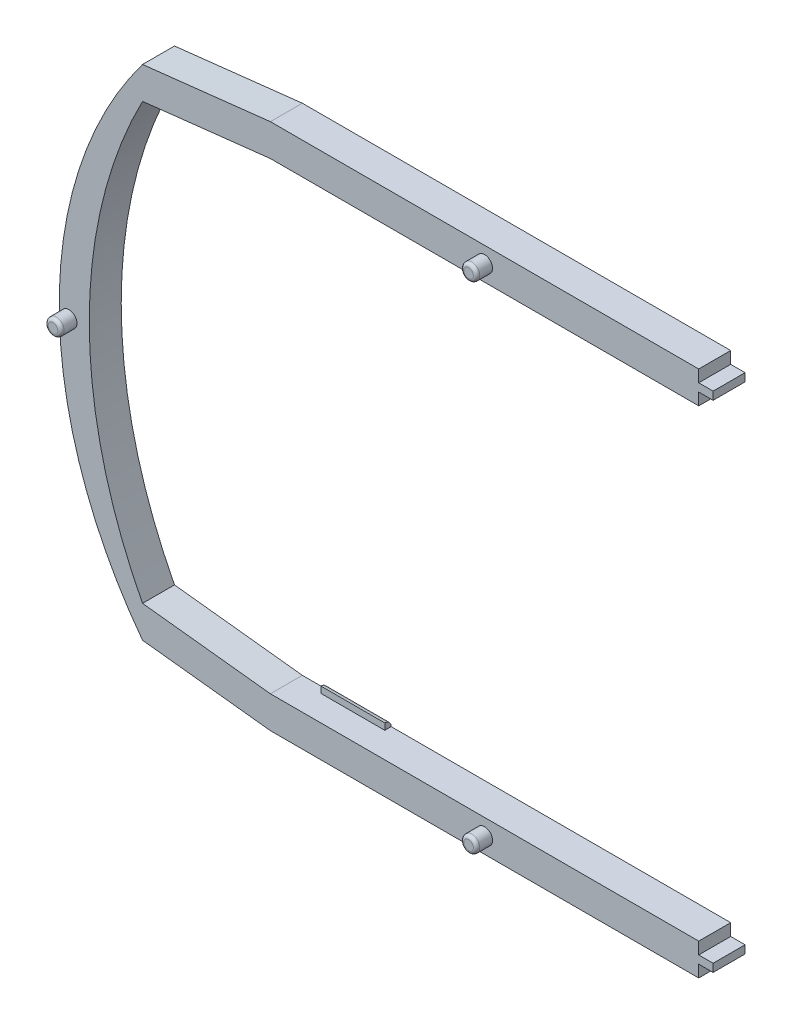
SolidWorks part; units mm, degrees
ref_plane "Plan de face" through (0, 0, 0) normal (0, 0, 1) x (1, 0, 0)
ref_plane "Plan de dessus" through (0, 0, 0) normal (0, 1, 0) x (1, 0, 0)
ref_plane "Plan de droite" through (0, 0, 0) normal (1, 0, 0) x (0, 0, -1)
sketch "Esquisse1" plane through (0, 0, 0) normal (0, 0, 1) x (1, 0, 0)
  line L0 (-191.5944, 34.0601) -> (-151.5944, 38.5601)
  line L1 (-151.5944, 38.5601) -> (-17.5944, 38.5601)
  line L2 (-151.5944, 38.5601) -> (-151.5944, -106.4399)
  line L3 (-151.5944, -106.4399) -> (-17.5944, -106.4399)
  line L4 (-17.5944, 38.5601) -> (-17.5944, -106.4399)
  line L5 (-151.5944, 38.5601) -> (-191.5944, 38.5601)
  line L6 (-151.5944, 48.5601) -> (-151.5944, -106.4399)
  line L7 (-151.5944, 38.5601) -> (-151.5944, -106.4399)
  line L8 (-151.5944, -106.4399) -> (-191.5944, -106.4399)
  line L9 (-191.5944, 38.5601) -> (-191.5944, -106.4399)
  line L10 (-151.5944, 38.5601) -> (-191.5944, 38.5601)
  line L11 (-151.5944, 38.5601) -> (-151.5944, 34.0601)
  line L12 (-151.5944, 34.0601) -> (-191.5944, 34.0601)
  line L13 (-191.5944, 38.5601) -> (-191.5944, 34.0601)
  line L14 (-151.5944, -106.4399) -> (-191.5944, -106.4399)
  line L15 (-151.5944, -106.4399) -> (-151.5944, -101.9399)
  line L16 (-151.5944, -101.9399) -> (-191.5944, -101.9399)
  line L17 (-191.5944, -106.4399) -> (-191.5944, -101.9399)
  line L18 (-191.5944, -101.9399) -> (-151.5944, -106.4399)
  line L19 (-151.5944, 48.5601) -> (-191.5944, 44.0601)
  line L20 (-151.5944, 38.5601) -> (-17.5944, 38.5601)
  line L21 (-151.5944, 38.5601) -> (-151.5944, 48.5601)
  line L22 (-151.5944, 48.5601) -> (-17.5944, 48.5601)
  line L23 (-17.5944, 38.5601) -> (-17.5944, 48.5601)
  line L24 (-143.8059, 38.5601) -> (-123.8059, 38.5601)
  line L25 (-143.8059, 38.5601) -> (-143.8059, 36.5601)
  line L26 (-143.8059, 36.5601) -> (-123.8059, 36.5601)
  line L27 (-123.8059, 38.5601) -> (-123.8059, 36.5601)
  line L28 (-143.8059, -106.4399) -> (-123.8059, -106.4399)
  line L29 (-143.8059, -106.4399) -> (-143.8059, -104.4399)
  line L30 (-143.8059, -104.4399) -> (-123.8059, -104.4399)
  line L31 (-123.8059, -106.4399) -> (-123.8059, -104.4399)
  line L32 (-151.5944, -106.4399) -> (-17.5944, -106.4399)
  line L33 (-151.5944, -106.4399) -> (-151.5944, -116.4399)
  line L34 (-151.5944, -116.4399) -> (-17.5944, -116.4399)
  line L35 (-17.5944, -106.4399) -> (-17.5944, -116.4399)
  line L36 (-191.5944, 44.0601) -> (-191.5944, 34.0601)
  line L37 (-191.5944, 44.0601) -> (-191.5944, 38.5601)
  line L38 (-151.5944, -116.4399) -> (-191.5944, -111.9399)
  line L39 (-191.5944, -111.9399) -> (-191.5944, -106.4399)
  line L41 (-13.0944, 44.8101) -> (-17.5944, 44.8101)
  line L42 (-13.0944, 44.8101) -> (-13.0944, 42.3101)
  line L43 (-13.0944, 42.3101) -> (-17.5944, 42.3101)
  line L44 (-17.5944, 44.8101) -> (-17.5944, 42.3101)
  line L45 (-13.0944, -110.1899) -> (-17.5944, -110.1899)
  line L46 (-13.0944, -110.1899) -> (-13.0944, -112.6899)
  line L47 (-13.0944, -112.6899) -> (-17.5944, -112.6899)
  line L48 (-17.5944, -110.1899) -> (-17.5944, -112.6899)
  arc A0 (-191.5944, -111.9399) -> (-191.5944, 44.0601) centre (-87.9148, -33.9399) cw
  arc A1 (-191.5944, -101.9399) -> (-191.5944, 34.0601) centre (-61.1863, -33.9399) cw
  circle A2 centre (-214.5939, -36.3632) radius 2.5
  circle A4 centre (-84.5944, -111.4399) radius 2.5
  circle A5 centre (-84.5944, 43.5601) radius 2.5
  point P11 (-209.5944, -36.4399)
  point P15 (-219.5941, -36.3611)
  dimension "D10" = 10
  dimension "D19" = 5
  dimension "D1" = 134
  dimension "D2" = 145
  dimension "D3" = 40
  dimension "D4" = 4.5
  dimension "D5" = 4.5
  dimension "D6" = 18
  dimension "D7" = 75
  dimension "D8" = 67
  dimension "D9" = 67
  dimension "D11" = 10
  dimension "D12" = 10
  dimension "D13" = 48
  dimension "D14" = 2
  dimension "D15" = 20
  dimension "D16" = 20
  dimension "D17" = 2
  dimension "D18" = 48
  dimension "D20" = 10
  dimension "D21" = 5
  dimension "D22" = 5
  dimension "D23" = 10
  dimension "D24" = 2.5
  dimension "D25" = 3.75
  dimension "D26" = 2.5
  dimension "D27" = 3.75
  dimension "D28" = 4.5
  dimension "D29" = 4.5
extrude "Boss.-Extru.2" add sketch "Esquisse1" along normal blind 10 contours L1 L20 L23 L22 L6 A5 | L19 L36 L5 L6 | L9 A1 L36 A0 L39 A2 | L5 L9 L0 | L39 L38 L33 L8 | L18 L9 L8 | L35 L3 L33 L34 A4 region at (-178.2611, 37.0601, 0) region at (-209.8403, -33.9399, 0) region at (-150.2507, 43.5601, 0) region at (-169.659, 42.544, 0) region at (-178.2611, -104.9399, 0) region at (-169.659, -110.4238, 0) region at (-147.7002, -107.7836, 0)
extrude "Boss.-Extru.3" add sketch "Esquisse1<26>" along normal blind 2 contours L3 L31 L30 L29 | L26 L27 L24 L25 region at (-133.8059, -105.4399, 0)
sketch "Esquisse1<26>" plane through (0, 0, 0) normal (0, 0, 1) x (1, 0, 0) same geometry as "Esquisse1"
extrude "Boss.-Extru.4" add sketch "Esquisse1<27>" along normal blind 15 contours A2 | A5 | A4 region at (-214.5939, -36.3632, 0) region at (-84.5944, -111.4399, 0) region at (-84.5944, 43.5601, 0)
sketch "Esquisse1<27>" plane through (0, 0, 0) normal (0, 0, 1) x (1, 0, 0) same geometry as "Esquisse1"
extrude "Boss.-Extru.5" add sketch "Esquisse1<28>" along normal blind 10 contours L43 L42 L41 L23 | L47 L46 L45 L35 region at (-15.3444, 43.5601, 0) region at (-15.3444, -111.4399, 0)
sketch "Esquisse1<28>" plane through (0, 0, 0) normal (0, 0, 1) x (1, 0, 0) same geometry as "Esquisse1"
fillet "Congé1" radius 1 1 edges at (-82.0944, 43.5601, 15)
fillet "Congé2" radius 1 1 edges at (-82.0944, -111.4399, 15)
fillet "Congé3" radius 1 1 edges at (-212.0939, -36.3632, 15)
fillet "Congé4" radius 2 1 edges at (-133.8059, -104.4399, 0)
fillet "Congé5" radius 2 1 edges at (-133.8059, 36.5601, 0)
